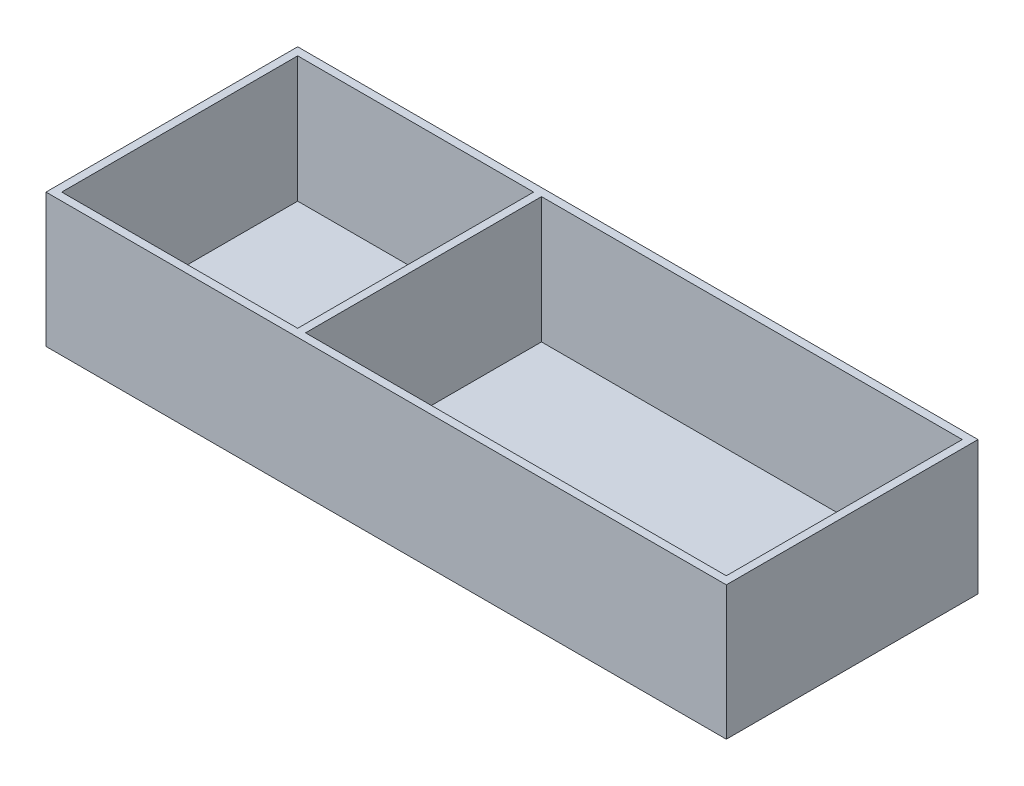
SolidWorks part; units mm, degrees
ref_plane "Front" through (0, 0, 0) normal (0, 0, 1) x (1, 0, 0)
ref_plane "Top" through (0, 0, 0) normal (0, 1, 0) x (1, 0, 0)
ref_plane "Right" through (0, 0, 0) normal (1, 0, 0) x (0, 0, -1)
sketch "Sketch1" plane through (0, 0, 0) normal (0, 1, 0) x (1, 0, 0)
  line L1 (-86.5, -32) -> (86.5, -32)
  line L2 (-86.5, -32) -> (-86.5, 32)
  line L3 (-86.5, 32) -> (86.5, 32)
  line L4 (86.5, -32) -> (86.5, 32)
  line L5 (-86.5, -32) -> (86.5, 32) construction
  line L6 (-86.5, 32) -> (86.5, -32) construction
  point P0 (0, 0)
  dimension "D1" = 64
  dimension "D2" = 173
extrude "Boss-Extrude1" add sketch "Sketch1" along normal blind 34
shell "Shell1" thickness 2 removed face at (0, 34, 0)
sketch "Sketch3" plane through (0, 2, 0) normal (0, 1, 0) x (1, 0, 0)
  line L0 (84.5, 30) -> (-84.5, 30) construction
  line L1 (-24.5, -30) -> (-22.5, -30)
  line L2 (-24.5, -30) -> (-24.5, 30)
  line L3 (-24.5, 30) -> (-22.5, 30)
  line L4 (-22.5, -30) -> (-22.5, 30)
  line L5 (-24.5, -30) -> (-22.5, 30) construction
  line L6 (-24.5, 30) -> (-22.5, -30) construction
  line L7 (-84.5, 30) -> (-84.5, -30) construction
  point P0 (-23.5, 0)
  dimension "D1" = 2
  dimension "D2" = 60
extrude "Boss-Extrude2" add sketch "Sketch3" along normal up to vertex (32 mm away) up to point (84.5, 34, -30)
